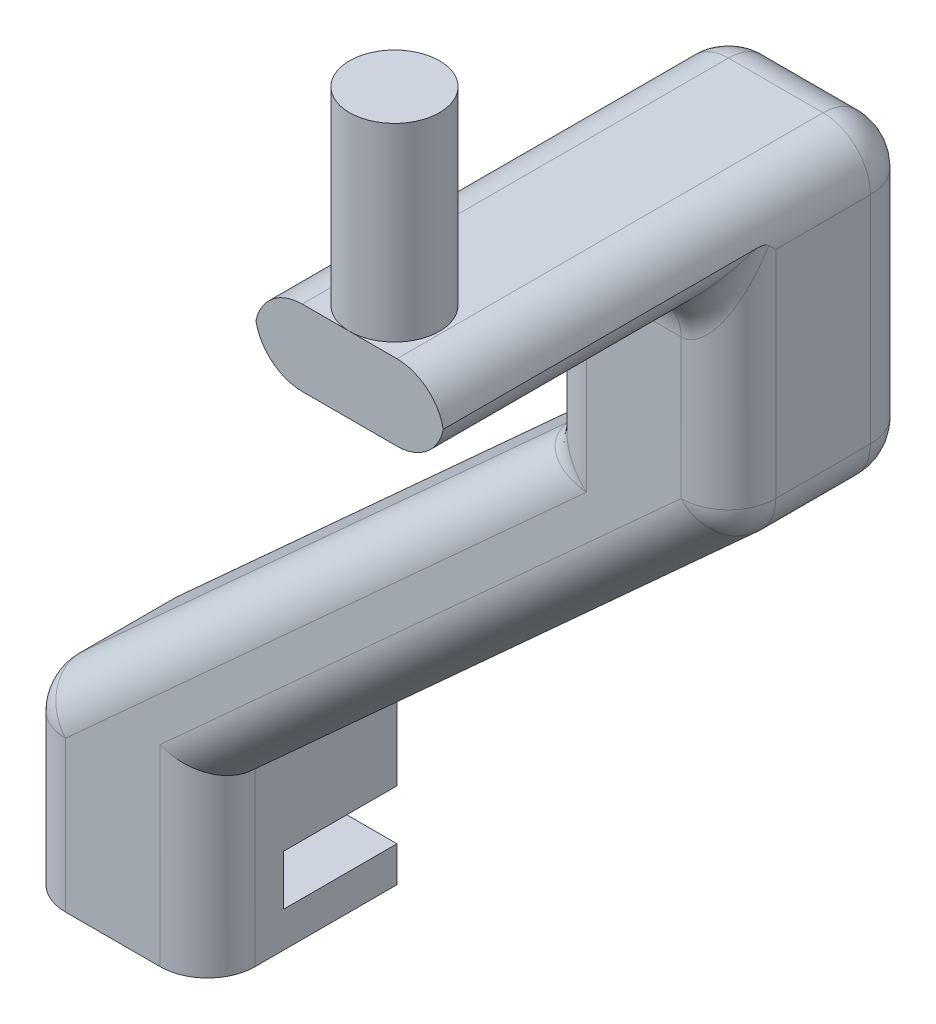
SolidWorks part; units mm, degrees
ref_plane "Plan de face" through (0, 0, 0) normal (0, 0, 1) x (1, 0, 0)
ref_plane "Plan de dessus" through (0, 0, 0) normal (0, 1, 0) x (1, 0, 0)
ref_plane "Plan de droite" through (0, 0, 0) normal (1, 0, 0) x (0, 0, -1)
sketch "Esquisse1" plane through (0, 0, 0) normal (0, 0, 1) x (1, 0, 0)
  line L0 (2.7111, 68.1053) -> (-52.2889, 18.1053)
  line L1 (-52.2889, 18.1053) -> (-32.2889, 18.1053)
  line L2 (-52.2889, 18.1053) -> (-52.2889, 0)
  line L3 (-52.2889, 0) -> (-32.2889, 0)
  line L4 (-32.2889, 18.1053) -> (-32.2889, 0)
  line L5 (2.7111, 98.1053) -> (22.7111, 98.1053)
  line L6 (2.7111, 98.1053) -> (2.7111, 68.1053)
  line L7 (2.7111, 68.1053) -> (22.7111, 68.1053)
  line L8 (22.7111, 98.1053) -> (22.7111, 68.1053)
  line L9 (22.7111, 68.1053) -> (-32.2889, 18.1053)
  dimension "D1" = 20
  dimension "D2" = 20
  dimension "D3" = 30
  dimension "D4" = 35
  dimension "D5" = 50
extrude "Boss.-Extru.2" add sketch "Esquisse1" along normal blind 20 contours L8 L5 L6 L7 | L9 L7 L0 L1 | L4 L1 L2 L3 region at (-14.7889, 43.1053, 0) region at (12.7111, 83.1053, 0) region at (-42.2889, 9.0526, 0)
sketch "Esquisse3" plane through (0, 0, 0) normal (1, 0, 0) x (0, 0, -1)
  line L0 (0, 18.1053) -> (0, 0) construction
  line L1 (0, 9.0479) -> (-12, 9.0479)
  line L2 (0, 9.0479) -> (0, 3.7479)
  line L3 (0, 3.7479) -> (-12, 3.7479)
  line L4 (-12, 9.0479) -> (-12, 3.7479)
  dimension "D1" = 12
  dimension "D2" = 5.3
extrude "Enlèv. mat.-Extru.1" cut sketch "Esquisse3" against normal blind 60
sketch "Esquisse4" plane through (0, 0, 0) normal (0, 0, 1) x (1, 0, 0)
  line L0 (22.7111, 98.1053) -> (22.7111, 68.1053) construction
  line L1 (2.7111, 98.1053) -> (22.7111, 98.1053)
  line L2 (2.7111, 98.1053) -> (2.7111, 90.1053)
  line L3 (2.7111, 90.1053) -> (22.7111, 90.1053)
  line L4 (22.7111, 98.1053) -> (22.7111, 90.1053)
  dimension "D1" = 8
extrude "Boss.-Extru.3" add sketch "Esquisse4" along normal blind 50
sketch "Esquisse5" plane through (0, 98.1053, 2.0038) normal (0, 1, 0) x (1, 0, 0)
  line L0 (22.7111, -47.9962) -> (2.7111, -47.9962) construction
  circle A0 centre (12.7, -43.2462) radius 4.75
  point P4 (12.7111, -47.9962)
  dimension "D1" = 9.5
  dimension "D2" = 4.75
extrude "Boss.-Extru.4" add sketch "Esquisse5" along normal blind 20 separate body
fillet "Congé3" radius 5 1 edges at (-24.7889, 43.1053, 20)
fillet "Congé4" radius 5 1 edges at (2.7111, 75.7266, 20)
fillet "Congé5" radius 5 1 edges at (2.7111, 90.1053, 32.5)
fillet "Congé7" radius 5 4 edges at (-4.7889, 43.1053, 0) (22.7111, 83.1053, 0) (2.7111, 83.1053, 0) (-24.7889, 43.1053, 0)
fillet "Congé8" radius 5 8 edges at (2.7111, 98.1053, 27.5) (4.1756, 98.1053, 1.4645) (12.7111, 98.1053, 0) (21.2467, 98.1053, 1.4645) (22.7111, 98.1053, 27.5) (22.7111, 90.1053, 35) (22.7111, 79.1053, 20) (-4.7889, 43.1053, 20)
fillet "Congé10" radius 5 6 edges at (20.8734, 91.2323, 18.873) (12.7111, 90.1053, 20) (4.5489, 91.2323, 18.873) (4.1756, 67.4574, 18.5355) (4.1756, 67.4574, 1.4645) (2.7111, 68.1053, 10)
fillet "Congé11" radius 5 3 edges at (21.2467, 68.7531, 1.4645) (22.7111, 68.1053, 10) (21.2467, 68.7531, 18.5355)
fillet "Congé13" radius 5 6 edges at (-52.2889, 10.1979, 0) (-52.2889, 16.1261, 1.4645) (-52.2889, 18.1053, 10) (-52.2889, 16.1261, 18.5355) (-32.2889, 12.4313, 20) (-52.2889, 5.674, 20)
